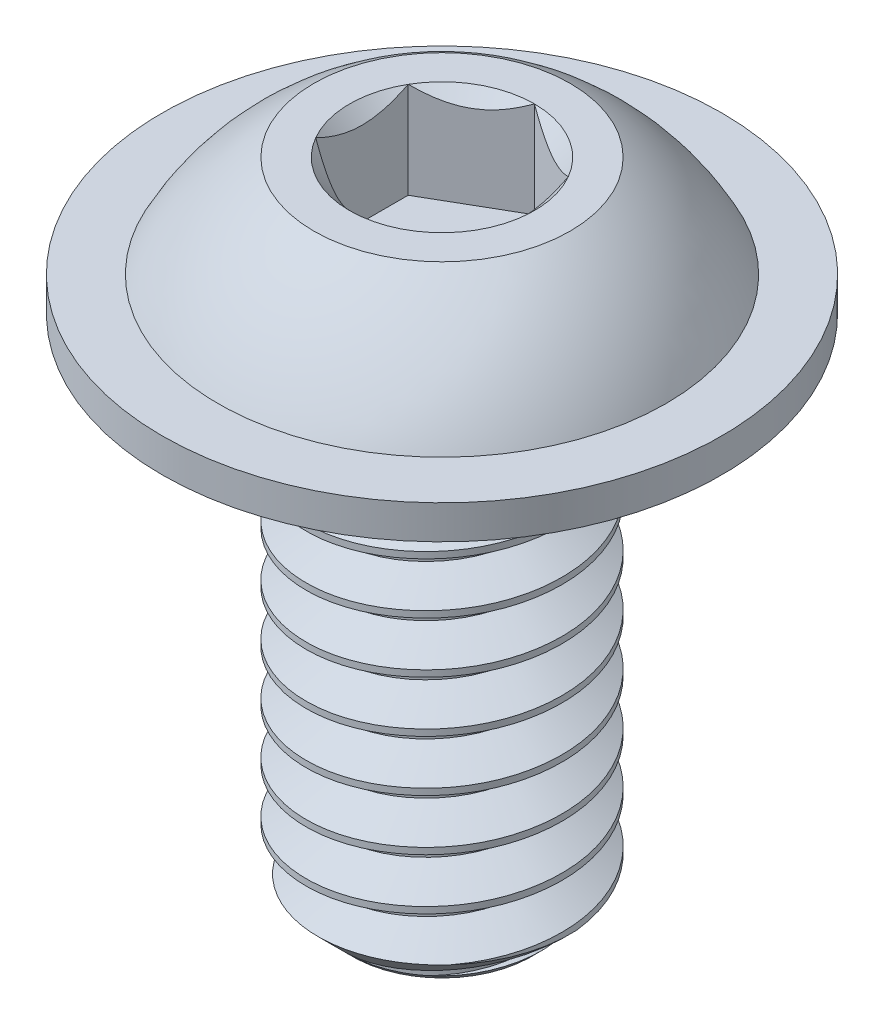
SolidWorks part; units mm, degrees
ref_plane "Front Plane" through (0, 0, 0) normal (0, 0, 1) x (1, 0, 0)
ref_plane "Top Plane" through (0, 0, 0) normal (0, 1, 0) x (1, 0, 0)
ref_plane "Right Plane" through (0, 0, 0) normal (1, 0, 0) x (0, 0, -1)
sketch "Sketch1" plane through (0, 0, 0) normal (0, 1, 0) x (1, 0, 0)
  line L0 (-12.7, 0) -> (12.7, 0) construction
  circle A0 centre (-12.7, 0) radius 3.175
  point P3 (-15.875, 0)
  point P4 (-9.525, 0)
  dimension "D1" = 6.35
  dimension "D2" = 25.4
extrude "Boss-Extrude1" add sketch "Sketch1" against normal blind 12.7
sketch "Sketch2" plane through (0, -12.7, 0) normal (0, -1, 0) x (1, 0, 0)
  circle A1 centre (-12.7, 0) radius 3.175
  circle A2 centre (-12.7, 0) radius 3.175
  point P0 (-12.7, -3.175)
  dimension "D1" = 0
curve "Helix/Spiral1" pitch 1.27 height 13.97 turns 11
ref_plane "Plane1" through (-12.7, 0, 0) normal (1, 0, 0) x (0, 0, -1)
sketch "Sketch3" plane through (-12.7, 0, 0) normal (1, 0, 0) x (0, 0, -1)
  line L0 (3.3125, -12.6206) -> (2.2126, -13.2556) construction
  line L1 (2.2126, -13.2556) -> (3.3125, -13.8906) construction
  line L2 (3.3125, -13.8906) -> (3.3125, -12.6206) construction
  line L3 (2.3501, -13.1762) -> (2.3501, -13.335) construction
  line L4 (3.175, -12.7) -> (3.175, -13.8112) construction
  line L5 (2.2126, -13.2556) -> (2.3501, -13.2556) construction
  line L6 (3.175, -13.2556) -> (3.3125, -13.2556) construction
  line L8 (2.2126, -13.2556) -> (-3.175, -13.2556) construction
  line L9 (2.3501, -13.1762) -> (3.2437, -12.6603)
  line L10 (2.3501, -13.1762) -> (2.3501, -13.335)
  line L11 (2.3501, -13.335) -> (3.2437, -13.8509)
  line L12 (3.2437, -13.8509) -> (3.2437, -12.6603)
  line L14 (-3.175, -13.2556) -> (-3.175, -11.9856) construction
  line L15 (-3.175, -11.9856) -> (-3.175, -10.7156) construction
  line L16 (-3.175, -10.7156) -> (-3.175, -9.4456) construction
  line L17 (-3.175, -9.4456) -> (-3.175, -8.1756) construction
  line L18 (-3.175, 0) -> (-3.175, -12.7) construction
  point P15 (3.2437, -13.2556)
  dimension "D1" = 1.27
  dimension "D2" = 0.1588
sweep "Cut-Sweep1" cut profiles "Sketch3" path "Helix/Spiral1"
sketch "Sketch4" plane through (0, -12.7, 0) normal (0, -1, 0) x (1, 0, 0)
  circle A0 centre (-12.7, 0) radius 2.2126
extrude "Cut-Extrude1" cut sketch "Sketch4" against normal blind 1.27 draft 45 flip side to cut
sketch "Sketch5" plane through (0, 0, 0) normal (0, 0, 1) x (1, 0, 0)
  line L0 (-12.7, 0) -> (-12.7, 3.3528)
  line L1 (-19.6342, 0) -> (-12.7, 0)
  line L2 (-12.7, 3.3528) -> (-15.875, 3.3528)
  line L3 (-18.2499, 0.8382) -> (-19.6342, 0.8382)
  line L4 (-19.6342, 0.8382) -> (-19.6342, 0)
  line L5 (-12.7, 0) -> (-12.7, -12.7) construction
  arc A0 (-15.875, 3.3528) -> (-18.2499, 0.8382) centre (-12.7, -2.0246) ccw
  dimension "D1" = 3.3528
  dimension "D2" = 0.8382
  dimension "D3" = 13.8684
  dimension "D4" = 11.0998
revolve "Revolve1" add sketch "Sketch5" angle 360 mid plane about L0
sketch "Sketch6" plane through (0, 3.3528, 0) normal (0, 1, 0) x (1, 0, 0)
  line L1 (-12.7, 2.2914) -> (-14.6844, 1.1457)
  line L2 (-14.6844, 1.1457) -> (-14.6844, -1.1457)
  line L3 (-14.6844, -1.1457) -> (-12.7, -2.2914)
  line L4 (-12.7, -2.2914) -> (-10.7156, -1.1457)
  line L5 (-10.7156, -1.1457) -> (-10.7156, 1.1457)
  line L6 (-10.7156, 1.1457) -> (-12.7, 2.2914)
  circle A0 centre (-12.7, 0) radius 1.9844 construction
  dimension "D1" = 3.9688
extrude "Cut-Extrude2" cut sketch "Sketch6" against normal blind 2.3813
sketch "Sketch7" plane through (0, 3.3528, 0) normal (0, 1, 0) x (1, 0, 0)
  circle A0 centre (-12.7, 0) radius 2.2914
extrude "Cut-Extrude3" cut sketch "Sketch7" against normal blind 2.3813 draft 45
move or copy body "Body-Move/Copy1" bodies to move or copy 110 copy yes number of copies 1 translate (25.4, 0, 0)
sketch "Sketch8" plane through (0, 0, 0) normal (0, 1, 0) x (1, 0, 0)
  line L0 (-23.8125, 0) -> (23.8125, 0) construction
  line L1 (-21.4742, 5.6261) -> (21.4742, 5.6261)
  line L2 (-21.4742, -5.6261) -> (21.4742, -5.6261)
  line L4 (-23.8125, 5.6261) -> (23.8125, 5.6261) construction
  line L5 (-23.8125, 5.6261) -> (-23.8125, -5.6261) construction
  line L6 (-23.8125, -5.6261) -> (23.8125, -5.6261) construction
  line L7 (23.8125, 5.6261) -> (23.8125, -5.6261) construction
  arc A0 (-21.4742, 5.6261) -> (-21.4742, -5.6261) centre (-15.875, 0) ccw
  arc A1 (21.4742, 5.6261) -> (21.4742, -5.6261) centre (15.875, 0) cw
  circle A3 centre (-12.7, 0) radius 3.175
  circle A4 centre (-12.7, 0) radius 3.175
  circle A5 centre (12.7, 0) radius 3.175
  dimension "D2" = 47.625
  dimension "D4" = 7.9375
  dimension "D3" = 11.2522
  dimension "D1" = 0
extrude "Boss-Extrude2" add sketch "Sketch8" against normal blind 2.3876 from offset 6.35 separate body offset against normal yes
sketch "Sketch9" plane through (0, -8.7376, 0) normal (0, -1, 0) x (1, 0, 0)
  circle A0 centre (12.7, 0) radius 3.175
  circle A1 centre (-12.7, 0) radius 3.175 construction
  circle A2 centre (-12.7, 0) radius 3.175
  circle A3 centre (-12.7, 0) radius 3.5687
  circle A4 centre (12.7, 0) radius 3.5687
  dimension "D1" = 7.1374
extrude "Boss-Extrude3" add sketch "Sketch9" along normal blind 0.762
sketch "SketchZ" plane through (0, 0, 0) normal (0, 0, 1) x (1, 0, 0)
  line L0 (-9.525, -12.9381) -> (-9.525, -11.6681) construction
  line L2 (-12.7, -13.2556) -> (-12.7, -11.9856) construction
  line L4 (-9.525, -12.9381) -> (-12.7, -12.9381) construction
  line L5 (-12.7, -9.4456) -> (-12.7, -8.1756) construction
  line L6 (-12.7, -12.6206) -> (-12.7, -13.2556) construction
delete or keep bodies "Body-Delete/Keep 1" type delete bodies bodies 136
delete or keep bodies "Body-Delete/Keep 2" type delete bodies bodies 135
equation "\"D3@Helix/Spiral1\" = \"D4@Helix/Spiral1\" + \"D1@Boss-Extrude1\""
equation "\"D1@Sketch3\" = \"D4@Helix/Spiral1\""
equation "\"D2@Sketch3\" = \"D1@Sketch3\" / 8"
equation "\"D1@Cut-Extrude1\" = \"D4@Helix/Spiral1\""
equation "\"D1@Cut-Extrude2\" = \"D1@Sketch6\" * 3/5"
equation "\"D1@Cut-Extrude3\" = \"D1@Cut-Extrude2\""
equation "\"D2@Sketch5\" = \"D1@Sketch5\" * 1/4"
